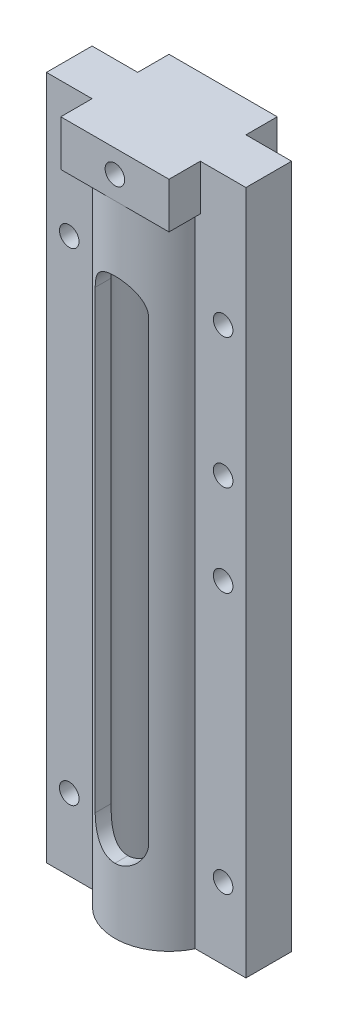
SolidWorks part; units mm, degrees
ref_plane "Front Plane" through (0, 0, 0) normal (0, 0, 1) x (1, 0, 0)
ref_plane "Top Plane" through (0, 0, 0) normal (0, 1, 0) x (1, 0, 0)
ref_plane "Right Plane" through (0, 0, 0) normal (1, 0, 0) x (0, 0, -1)
sketch "Sketch1" plane through (0, 0, 0) normal (0, 1, 0) x (1, 0, 0)
  circle A0 centre (0, 0) radius 6.3
  circle A1 centre (0, 0) radius 8.3
  dimension "D1" = 12.6
  dimension "D2" = 16.6
extrude "Boss-Extrude1" add sketch "Sketch1" along normal blind 95
sketch "Sketch3" plane through (0, 95, 0) normal (0, 1, 0) x (1, 0, 0)
  circle A1 centre (0, 0) radius 8.3
extrude "Boss-Extrude2" add sketch "Sketch3" along normal blind 3
sketch "Sketch4" plane through (0, 95, 0) normal (0, -1, 0) x (-1, 0, 0)
  circle A0 centre (0, 0) radius 1.5
  circle A1 centre (0, 0) radius 6.3
  dimension "D1" = 3
  dimension "D2" = 12.6
sketch "Sketch5" plane through (0, 98, 0) normal (0, 1, 0) x (1, 0, 0)
  line L1 (-8.3, 8.3) -> (8.3, 8.3)
  line L2 (-8.3, 8.3) -> (-8.3, -8.3)
  line L3 (-8.3, -8.3) -> (8.3, -8.3)
  line L4 (8.3, 8.3) -> (8.3, -8.3)
  line L5 (-8.3, 8.3) -> (8.3, -8.3) construction
  line L6 (-8.3, -8.3) -> (8.3, 8.3) construction
  point P0 (0, 0)
extrude "Boss-Extrude4" add sketch "Sketch5" along normal blind 7
sketch "Sketch6" plane through (0, 0, 8.3) normal (0, 0, 1) x (1, 0, 0)
  line L0 (0, 98) -> (0, 88)
  line L2 (0, 10) -> (-4.1, 10)
  line L3 (-4.1, 10) -> (-4.1, 88)
  line L4 (-4.1, 88) -> (4.1, 88)
  line L5 (4.1, 88) -> (4.1, 10)
  line L6 (4.1, 10) -> (0, 10)
  dimension "D1" = 10
  dimension "D2" = 78
  dimension "D3" = 4.1
  dimension "D4" = 8.2
extrude "Cut-Extrude1" cut sketch "Sketch6" against normal through all contours L6 L5 L4 L3 L2 region at (0, 49, 8.3)
fillet "Fillet1" radius 4.1 8 edges at (4.1, 88, -6) (4.1, 88, 6) (-4.1, 88, 6) (-4.1, 88, -6) (4.1, 10, -6) (4.1, 10, 6) (-4.1, 10, -6) (-4.1, 10, 6)
extrude "Cut-Extrude3" cut sketch "Sketch4" against normal blind 3
sketch "Sketch8" plane through (0, 95, 0) normal (0, -1, 0) x (-1, 0, 0)
  circle A0 centre (0, 0) radius 1.5
  dimension "D1" = 3
extrude "Boss-Extrude6" add sketch "Sketch8" along normal blind 2
sketch "Sketch9" plane through (-8.3, 0, 0) normal (-1, 0, 0) x (0, 0, 1)
  line L2 (0, 0) -> (3.5, 0)
  line L3 (3.5, 0) -> (3.5, 105)
  line L4 (3.5, 105) -> (-3.5, 105)
  line L5 (-3.5, 105) -> (-3.5, 0)
  line L6 (-3.5, 0) -> (0, 0)
  dimension "D1" = 3.5
  dimension "D2" = 7
extrude "Boss-Extrude7" add sketch "Sketch9" against normal up to next (2 mm away) and the other way blind 7
mirror "Mirror1" about plane through (0, 0, 0) normal (1, 0, 0) of "Boss-Extrude7"
hole_wizard "Ø3.0 (3) Diameter Hole1" positions "Sketch11" profile "Sketch12" hole size "Ø3.0" standard "ISO" end condition up to next
sketch "Sketch11" plane through (0, 0, 8.3) normal (0, 0, 1) x (1, 0, 0)
  point P0 (0, 101.5)
sketch "Sketch12" plane through (0, 101.5, 8.3) normal (1, 0, 0) x (0, -1, 0)
  line L0 (0, 0) -> (0, 16.6)
  line L1 (0, 16.6) -> (1.5, 16.6)
  line L2 (1.5, 16.6) -> (1.5, 0)
  line L5 (1.5, 0) -> (0, 0)
  line L11 (0, -6.35) -> (0, 107.95) construction
  dimension "Thru Hole Dia." = 3
  dimension "Thru Hole Depth" = 16.6
hole_wizard "Ø3.0 (3) Diameter Hole2" positions "Sketch13" profile "Sketch14" hole size "Ø3.0" standard "ISO" end condition through all
sketch "Sketch13" plane through (0, 0, 3.5) normal (0, 0, 1) x (1, 0, 0)
  line L0 (15.3, 105) -> (8.3, 105) construction
  point P0 (11.8, 85)
  point P4 (11.8, 11)
  point P11 (11.8, 105)
  dimension "D1" = 20
  dimension "D2" = 74
sketch "Sketch14" plane through (11.8, 85, 3.5) normal (1, 0, 0) x (0, -1, 0)
  line L0 (0, 0) -> (0, 11.8)
  line L1 (0, 11.8) -> (1.5, 11.8)
  line L2 (1.5, 11.8) -> (1.5, 0)
  line L5 (1.5, 0) -> (0, 0)
  line L11 (0, -6.35) -> (0, 107.95) construction
  dimension "Thru Hole Dia." = 3
  dimension "Thru Hole Depth" = 11.8
hole_wizard "Ø3.0 (3) Diameter Hole3" positions "Sketch15" profile "Sketch16" hole size "Ø3.0" standard "ISO" end condition through all
sketch "Sketch15" plane through (0, 0, -3.5) normal (0, 0, -1) x (-1, 0, 0)
  line L0 (-15.3, 105) -> (-8.3, 105) construction
  point P0 (-11.8, 65)
  point P5 (-11.8, 105)
  point P6 (-11.8, 51)
  dimension "D1" = 40
  dimension "D2" = 14
sketch "Sketch16" plane through (11.8, 65, -3.5) normal (1, 0, 0) x (0, 1, 0)
  line L0 (0, 0) -> (0, 11.8)
  line L1 (0, 11.8) -> (1.5, 11.8)
  line L2 (1.5, 11.8) -> (1.5, 0)
  line L5 (1.5, 0) -> (0, 0)
  line L11 (0, -6.35) -> (0, 107.95) construction
  dimension "Thru Hole Dia." = 3
  dimension "Thru Hole Depth" = 11.8
mirror "Mirror2" about plane through (0, 0, 0) normal (1, 0, 0) of "Ø3.0 (3) Diameter Hole2"
sketch "Sketch17" plane through (0, 0, 0) normal (0, -1, 0) x (-1, 0, 0)
  line L0 (15.3, 0) -> (4, 0)
  line L1 (15.3, 3.5) -> (15.3, -3.5) construction
  line L2 (-15.3, 0) -> (-4, 0)
  line L3 (-15.3, 3.5) -> (-15.3, -3.5) construction
  line L4 (15.3, 0) -> (15.3, -8.3)
  line L5 (15.3, -8.3) -> (-15.3, -8.3)
  line L6 (-15.3, -8.3) -> (-15.3, 8.3)
  line L7 (-15.3, 8.3) -> (15.3, 8.3)
  line L8 (15.3, 8.3) -> (15.3, 0)
  arc A0 (4, 0) -> (-4, 0) centre (0, 0) cw
  dimension "D1" = 4
  dimension "D2" = 4
